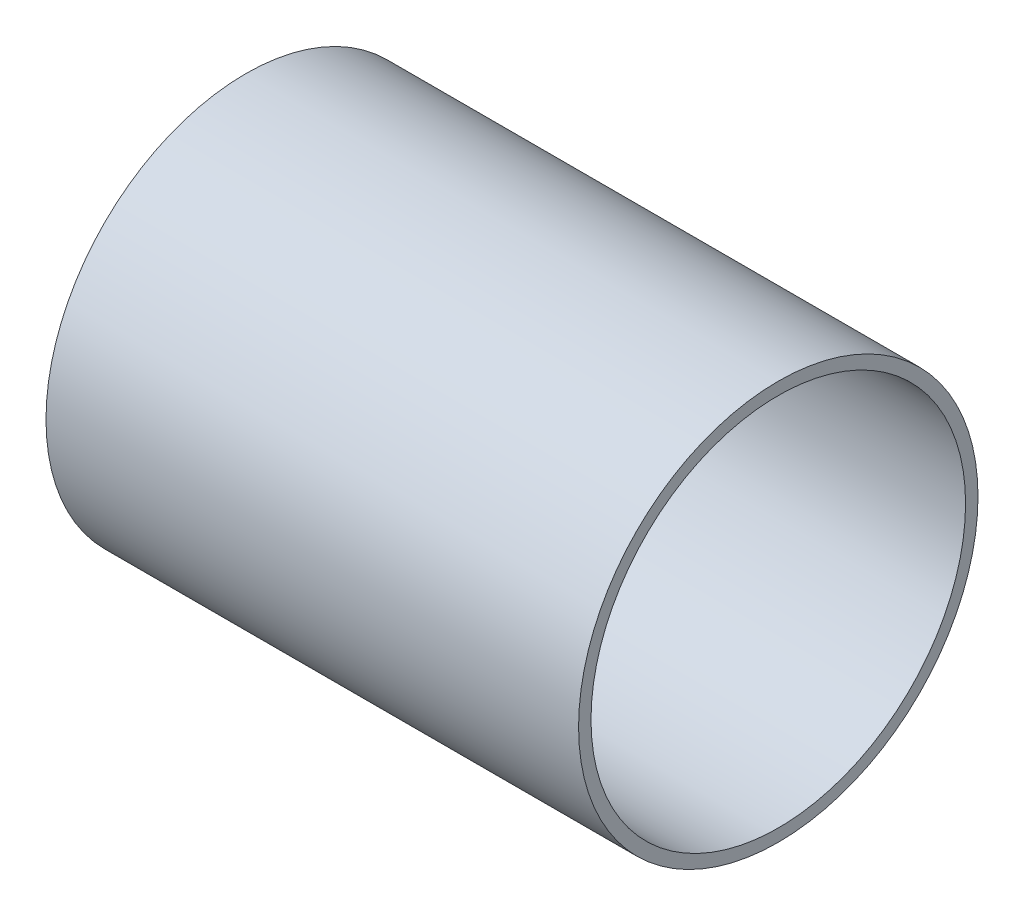
SolidWorks part; units mm, degrees
ref_plane "Front Plane" through (0, 0, 0) normal (0, 0, 1) x (1, 0, 0)
ref_plane "Top Plane" through (0, 0, 0) normal (0, 1, 0) x (1, 0, 0)
ref_plane "Right Plane" through (0, 0, 0) normal (1, 0, 0) x (0, 0, -1)
sketch "Sketch1" plane through (0, 0, 0) normal (1, 0, 0) x (0, 0, -1)
  circle A0 centre (0, 0) radius 14.2875
  circle A1 centre (0, 0) radius 13.3985
extrude "Boss-Extrude1" add sketch "Sketch1" along normal mid plane 38.1
